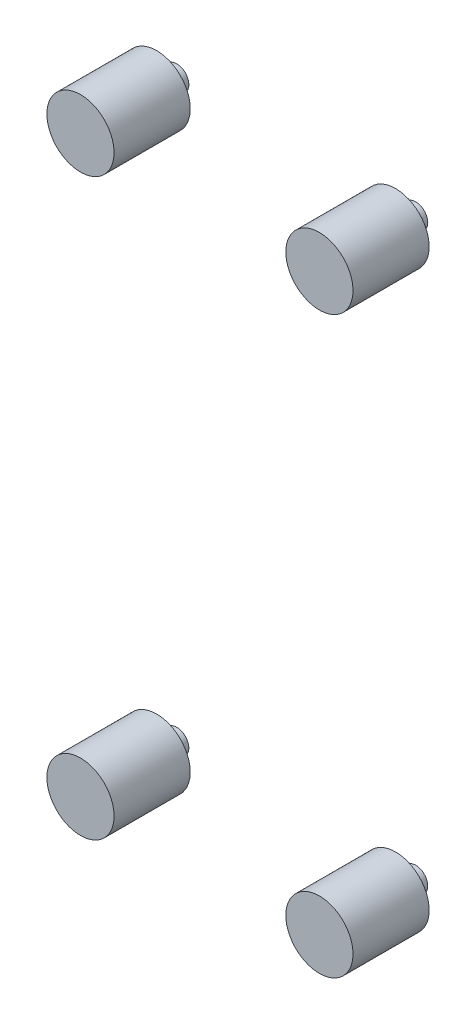
SolidWorks part; units mm, degrees
ref_plane "Front Plane" through (0, 0, 0) normal (0, 0, 1) x (1, 0, 0)
ref_plane "Top Plane" through (0, 0, 0) normal (0, 1, 0) x (1, 0, 0)
ref_plane "Right Plane" through (0, 0, 0) normal (1, 0, 0) x (0, 0, -1)
body saved out of another part "Stock-Enclosure^Shadowfang_Enclosure_V1-1" rebuild error yes
fillet "Fillet1" radius 1 rebuild error yes
sketch "Sketch1" plane through (0, 0, 8.5) normal (0, 0, -1) x (-1, 0, 0)
  circle A0 centre (-10.453, 25.6827) radius 3
  circle A1 centre (10.883, 25.6827) radius 3
  circle A2 centre (-10.453, -25.6253) radius 3
  circle A3 centre (10.883, -25.6253) radius 3
  dimension "D1" = 6
extrude "Boss-Extrude1" add sketch "Sketch1" along normal blind 6.8
sketch "Sketch2" plane through (0, 0, 1.7) normal (0, 0, -1) x (-1, 0, 0)
  circle A1 centre (10.883, 25.6827) radius 1.075
  circle A2 centre (-10.453, 25.6827) radius 1.075
  circle A3 centre (-10.453, -25.6253) radius 1.075
  circle A4 centre (10.883, -25.6253) radius 1.075
  dimension "D1" = 2.15
extrude "Boss-Extrude2" add sketch "Sketch2" along normal blind 1.8
sketch "Sketch3" plane through (0, 0, 10) normal (0, 0, 1) x (1, 0, 0)
  circle A0 centre (-16.215, 22.5287) radius 2.25
  circle A1 centre (15.785, 22.5287) radius 2.25
  circle A2 centre (-16.215, -22.4713) radius 2.25
  circle A3 centre (15.785, -22.4713) radius 2.25
  dimension "D1" = 4.5
extrude "Cut-Extrude1" cut sketch "Sketch3" against normal up to surface (5 mm away) rebuild error yes
sketch "Sketch4" plane through (0, 0, 10) normal (0, 0, 1) x (1, 0, 0)
  circle A0 centre (-16.215, 22.5287) radius 1.25
  circle A1 centre (15.785, 22.5287) radius 1.25
  circle A2 centre (15.785, -22.4713) radius 1.25
  circle A3 centre (-16.215, -22.4713) radius 1.25
  dimension "D1" = 2.5
extrude "Cut-Extrude2" cut sketch "Sketch4" against normal up to next rebuild error yes
